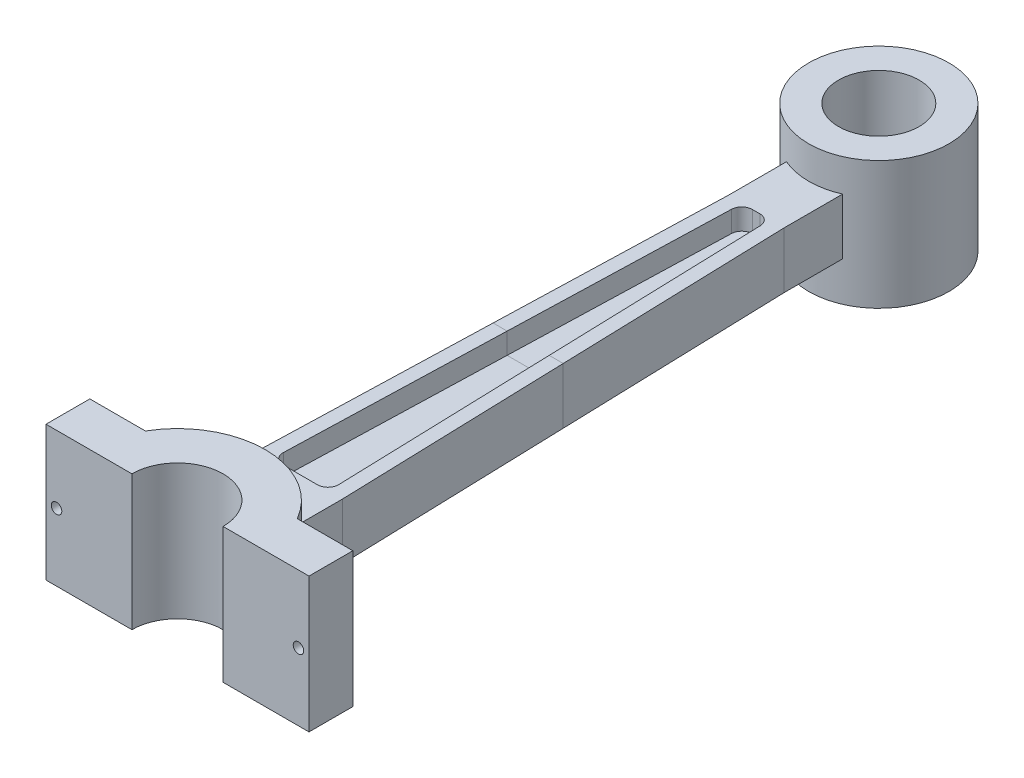
SolidWorks part; units mm, degrees
ref_plane "Front Plane" through (0, 0, 0) normal (0, 0, 1) x (1, 0, 0)
ref_plane "Top Plane" through (0, 0, 0) normal (0, 1, 0) x (1, 0, 0)
ref_plane "Right Plane" through (0, 0, 0) normal (1, 0, 0) x (0, 0, -1)
sketch "Sketch1" plane through (0, 0, 0) normal (0, 1, 0) x (1, 0, 0)
  line L0 (-50, -200) -> (50, -200)
  line L1 (0, -200) -> (0, 0) construction
  line L2 (0, 0) -> (0, 200) construction
  circle A0 centre (0, 200) radius 23
  arc A1 (50, -200) -> (-50, -200) centre (0, -200) ccw
  arc A2 (26, -200) -> (-26, -200) centre (0, -200) ccw
  circle A3 centre (0, 200) radius 40
  dimension "D1" = 50
  dimension "D2" = 46
  dimension "D3" = 26
  dimension "D5" = 80
  dimension "D4" = 400
extrude "Boss-Extrude1" add sketch "Sketch1" along normal blind 34.5 and the other way blind 38.5 contours A3 A0 region at (-38.8686, 0, -200)
extrude "Boss-Extrude2" add sketch "Sketch1<6>" along normal blind 38.5 and the other way blind 38.5 separate body contours A2 L0 A1 region at (0, 0, 151.118)
sketch "Sketch1<6>" plane through (0, 0, 0) normal (0, 1, 0) x (1, 0, 0) same geometry as "Sketch1"
ref_plane "Plane1" through (0, 0, 130) normal (0, 0, 1) x (1, 0, 0)
ref_plane "Plane2" through (0, 0, -130) normal (0, 0, 1) x (1, 0, 0)
sketch "Sketch2" plane through (0, 0, -130) normal (0, 0, 1) x (1, 0, 0)
  line L0 (16, 16) -> (8, 16)
  line L1 (8, 16) -> (8, 4)
  line L2 (8, 4) -> (-8, 4)
  line L3 (-8, 4) -> (-8, 16)
  line L4 (-8, 16) -> (-16, 16)
  line L5 (-16, 16) -> (-16, -16)
  line L6 (-16, 0) -> (0, 0) construction
  line L7 (0, 0) -> (16, 0) construction
  line L8 (16, -16) -> (16, 16)
  line L9 (16, -16) -> (8, -16)
  line L10 (8, -16) -> (8, -4)
  line L11 (-8, -4) -> (-8, -16)
  line L12 (8, -4) -> (-8, -4)
  line L13 (-8, -16) -> (-16, -16)
  dimension "D1" = 8
  dimension "D2" = 8
  dimension "D3" = 16
  dimension "D4" = 16
  dimension "D5" = 4
  dimension "D6" = 32
sketch "Sketch3" plane through (0, 0, 130) normal (0, 0, 1) x (1, 0, 0)
  line L0 (-24, -16) -> (-24, 16)
  line L1 (-24, 16) -> (-16, 16)
  line L2 (-16, 16) -> (-16, 4)
  line L3 (-16, 4) -> (16, 4)
  line L4 (16, 4) -> (16, 16)
  line L5 (16, 16) -> (24, 16)
  line L6 (24, 16) -> (24, -16)
  line L7 (40, 0) -> (-40, 0) construction
  line L8 (24, 0) -> (0, 0) construction
  line L9 (0, 0) -> (-24, 0) construction
  line L10 (16, -16) -> (24, -16)
  line L11 (16, -4) -> (16, -16)
  line L12 (-16, -4) -> (16, -4)
  line L13 (-16, -16) -> (-16, -4)
  line L14 (-24, -16) -> (-16, -16)
  dimension "D1" = 8
  dimension "D2" = 8
  dimension "D3" = 16
  dimension "D4" = 4
  dimension "D5" = 48
sketch "Sketch4" plane through (0, 0, 0) normal (0, 0, 1) x (1, 0, 0)
  line L0 (-20, 16) -> (-12, 16)
  line L1 (-12, 16) -> (-12, 4)
  line L2 (-12, 4) -> (12, 4)
  line L3 (12, 4) -> (12, 16)
  line L4 (12, 16) -> (20, 16)
  line L5 (20, 16) -> (20, -16)
  line L6 (20, 0) -> (0, 0) construction
  line L7 (0, 0) -> (-20, 0) construction
  line L8 (-20, -16) -> (-20, 16)
  line L9 (12, -16) -> (20, -16)
  line L10 (12, -4) -> (12, -16)
  line L11 (-12, -4) -> (12, -4)
  line L12 (-12, -16) -> (-12, -4)
  line L13 (-20, -16) -> (-12, -16)
  dimension "D1" = 8
  dimension "D2" = 8
  dimension "D3" = 4
  dimension "D4" = 40
  dimension "D5" = 16
loft "Loft1" add profiles "Sketch3", "Sketch4" connector at (-24, 16, 130) connector at (-20, 16, 0)
loft "Loft3" add profiles "Sketch4<3>", "Sketch2" connector at (-20, 16, 0) connector at (-16, 16, -130)
sketch "Sketch4<3>" plane through (0, 0, 0) normal (0, 0, 1) x (1, 0, 0) same geometry as "Sketch4"
extrude "Boss-Extrude4" add sketch "Sketch2<8>" against normal up to surface (48.4361 mm away) up to face at (0, -38.5, -177)
sketch "Sketch2<8>" plane through (0, 0, -130) normal (0, 0, 1) x (1, 0, 0) same geometry as "Sketch2"
extrude "Boss-Extrude5" add sketch "Sketch3<3>" along normal up to surface (60 mm away) up to face at (0, 0, 187)
sketch "Sketch3<3>" plane through (0, 0, 130) normal (0, 0, 1) x (1, 0, 0) same geometry as "Sketch3"
sketch "Sketch5" plane through (0, 0, 200) normal (0, 0, 1) x (1, 0, 0)
  line L0 (50, 38.5) -> (75, 38.5)
  line L1 (75, 38.5) -> (75, -38.5)
  line L2 (75, -38.5) -> (50, -38.5)
  line L3 (0, 0) -> (0, 38.5) construction
  line L4 (0, 38.5) -> (50, 38.5) construction
  line L6 (-75, -38.5) -> (-50, -38.5)
  line L7 (-75, 38.5) -> (-75, -38.5)
  line L8 (-50, 38.5) -> (-75, 38.5)
  line L9 (-50, 38.5) -> (-50, -38.5)
  line L10 (50, -38.5) -> (50, 38.5)
  line L11 (-50, 38.5) -> (-38, 38.5)
  line L12 (-50, 38.5) -> (-26, 38.5) construction
  line L13 (-38, 38.5) -> (-38, -38.5)
  line L14 (-50, -38.5) -> (-26, -38.5) construction
  line L15 (-38, -38.5) -> (-50, -38.5)
  line L16 (50, -38.5) -> (38, -38.5)
  line L17 (26, -38.5) -> (50, -38.5) construction
  line L18 (38, -38.5) -> (38, 38.5)
  line L19 (38, 38.5) -> (50, 38.5)
  circle A0 centre (69, 0) radius 3 construction
  circle A1 centre (69, 0) radius 3
  circle A2 centre (-69, 0) radius 3
  line M6 (50, -38.5) -> (50, 38.5)
  line M7 (50, 38.5) -> (26, 38.5)
  line M9 (26, -38.5) -> (50, -38.5)
extrude "Boss-Extrude6" add sketch "Sketch5" against normal blind 25 contours L2 L1 L0 A1 M6 | L18 M9 M6 M7 | L15 L13 L11 L9 | L9 L8 L7 L6 A2 region at (62.4031, 0, 200) region at (44, 0, 200) region at (-62.4031, 0, 200) region at (-44, 0, 200)
sketch "Sketch6" plane through (-16, 0, 0) normal (1, 0, 0) x (0, 0, -1)
  line L4 (-152.6291, 16) -> (-152.6291, 4)
  line L5 (-152.6291, 4) -> (-130, 4)
  line L6 (-130, 4) -> (-130, 16)
  line L7 (-130, 16) -> (-152.6291, 16)
  line L8 (-152.6291, 16) -> (-152.6291, 4)
  line L9 (-152.6291, 4) -> (-130, 4)
  line L10 (-130, 4) -> (-130, 16)
  line L11 (-130, 16) -> (-152.6291, 16)
  dimension "D1" = 0
extrude "Boss-Extrude7" add sketch "Sketch6" along normal blind 36
sketch "Sketch7" plane through (8, 0, 0) normal (-1, 0, 0) x (0, 0, 1)
  line L4 (-130, -4) -> (-160.8082, -4)
  line L5 (-160.8082, -4) -> (-160.8082, -16)
  line L6 (-160.8082, -16) -> (-130, -16)
  line L7 (-130, -16) -> (-130, -4)
  line L8 (-130, -4) -> (-160.8082, -4)
  line L9 (-160.8082, -4) -> (-160.8082, -16)
  line L10 (-160.8082, -16) -> (-130, -16)
  line L11 (-130, -16) -> (-130, -4)
  dimension "D1" = 0
extrude "Boss-Extrude8" add sketch "Sketch7" along normal blind 21
sketch "Sketch8" plane through (8, 0, 0) normal (-1, 0, 0) x (0, 0, 1)
  line L4 (-130, 16) -> (-160.8082, 16)
  line L5 (-160.8082, 16) -> (-160.8082, 4)
  line L6 (-160.8082, 4) -> (-130, 4)
  line L7 (-130, 4) -> (-130, 16)
  line L8 (-130, 16) -> (-160.8082, 16)
  line L9 (-160.8082, 16) -> (-160.8082, 4)
  line L10 (-160.8082, 4) -> (-130, 4)
  line L11 (-130, 4) -> (-130, 16)
  dimension "D1" = 0
extrude "Boss-Extrude9" add sketch "Sketch8" along normal blind 21
sketch "Sketch10" plane through (-24, 0, 0) normal (-1, 0, 0) x (0, 0, 1)
  line L4 (156.1366, -16) -> (156.1366, 16)
  line L5 (156.1366, 16) -> (130, 16)
  line L6 (130, 16) -> (130, -16)
  line L7 (130, -16) -> (156.1366, -16)
  line L8 (156.1366, -16) -> (156.1366, 16)
  line L9 (156.1366, 16) -> (130, 16)
  line L10 (130, 16) -> (130, -16)
  line L11 (130, -16) -> (156.1366, -16)
  dimension "D1" = 0
extrude "Boss-Extrude10" add sketch "Sketch10" against normal blind 46
fillet "Fillet4" radius 6 4 edges at (8, 10, -130) (-8, 10, -130) (-8, -10, -130) (8, -10, -130)
fillet "Fillet5" radius 6 4 edges at (-16, -10, 130) (16, -10, 130) (-16, 10, 130) (16, 10, 130)
